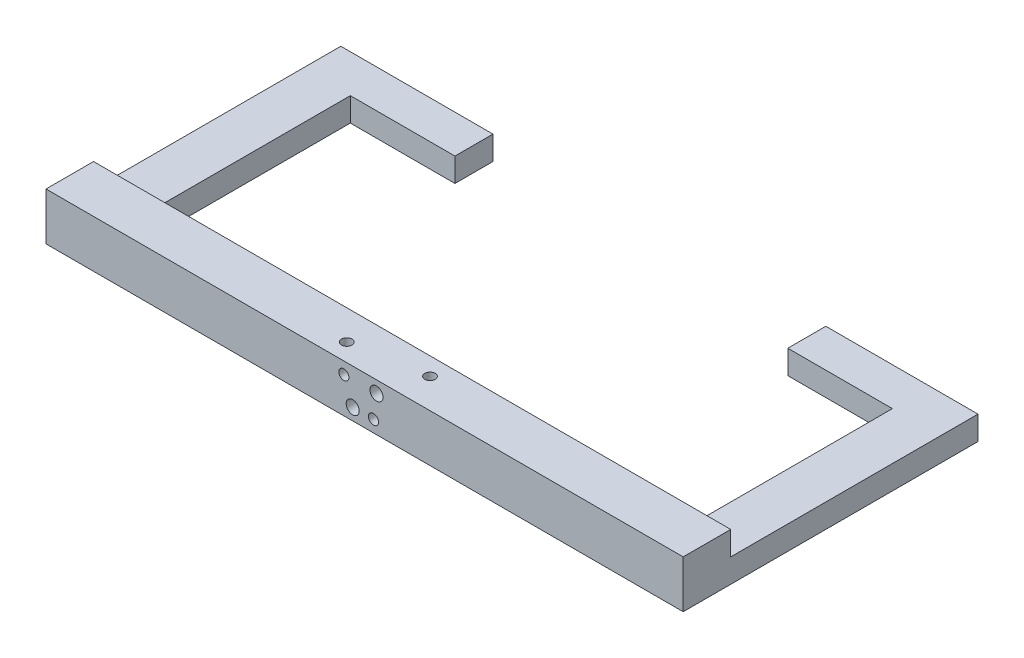
SolidWorks part; units mm, degrees
ref_plane "Front Plane" through (0, 0, 0) normal (0, 0, 1) x (1, 0, 0)
ref_plane "Top Plane" through (0, 0, 0) normal (0, 1, 0) x (1, 0, 0)
ref_plane "Right Plane" through (0, 0, 0) normal (1, 0, 0) x (0, 0, -1)
sketch "Sketch1" plane through (0, 0, 0) normal (0, 1, 0) x (1, 0, 0)
  line L0 (40.64, 68.58) -> (12.7, 68.58)
  line L7 (0, 78.74) -> (40.64, 78.74)
  line L8 (40.64, 68.58) -> (40.64, 78.74)
  line L9 (12.7, 68.58) -> (12.7, 12.7)
  line L10 (85.09, 68.0691) -> (85.09, -12.197) construction
  line L18 (12.7, 12.7) -> (157.48, 12.7)
  line L20 (0, 0) -> (170.18, 0)
  line L27 (0, 78.74) -> (0, 0)
  line L29 (170.18, 78.74) -> (170.18, 0)
  line L30 (157.48, 68.58) -> (157.48, 12.7)
  line L31 (129.54, 68.58) -> (129.54, 78.74)
  line L32 (170.18, 78.74) -> (129.54, 78.74)
  line L33 (129.54, 68.58) -> (157.48, 68.58)
  line L34 (97.79, 58.6145) -> (97.79, 33.6145) construction
  line L35 (72.39, 44.1997) -> (72.39, 23.8407) construction
  line L36 (12.7, 12.7) -> (0, 12.7)
  line L37 (157.48, 12.7) -> (170.18, 12.7)
  point P4 (85.09, 0)
  point P12 (85.09, 12.7)
  dimension "D1" = 10.16
  dimension "D2" = 157.48
  dimension "D3" = 55.88
  dimension "D4" = 12.7
  dimension "D5" = 40.64
  dimension "D6" = 12.7
  dimension "D7" = 12.7
  dimension "D8" = 12.7
extrude "Boss-Extrude2" add sketch "Sketch1" along normal blind 6.35 contours L18 L10 L20 L29 L32 L31 L33 L30 | L10 L18 L9 L0 L8 L7 L27 L20 region at (11.4884, 0, -52.7853) region at (158.6916, 0, -52.7853)
extrude "Boss-Extrude3" add sketch "Sketch1<3>" along normal blind 12.7 contours L37 L18 L36 L27 L20 L29 region at (85.09, 0, -6.35)
sketch "Sketch1<3>" plane through (0, 0, 0) normal (0, 1, 0) x (1, 0, 0) same geometry as "Sketch1"
sketch "Sketch3" plane through (0, 12.7, 0) normal (0, 1, 0) x (1, 0, 0)
  line L0 (0, 6.35) -> (170.18, 6.35) construction
  line L1 (0, 12.7) -> (0, 0) construction
  line L2 (170.18, 12.7) -> (170.18, 0) construction
  line L3 (0, 0) -> (170.18, 0) construction
  line L4 (72.39, 12.7) -> (97.79, 12.7) construction
  line L5 (72.39, 12.7) -> (72.39, 0) construction
  line L6 (72.39, 0) -> (97.79, 0) construction
  line L7 (97.79, 12.7) -> (97.79, 0) construction
  line L8 (72.39, 12.7) -> (97.79, 0) construction
  line L9 (72.39, 0) -> (97.79, 12.7) construction
  circle A0 centre (75.565, 7.9375) radius 1.397 construction
  circle A1 centre (94.615, 4.7625) radius 1.397 construction
  circle A2 centre (75.565, 4.7625) radius 1.397
  circle A3 centre (94.615, 7.9375) radius 1.397
  point P6 (85.09, 6.35)
  dimension "D2" = 2.794
  dimension "D1" = 25.4
  dimension "D3" = 3.175
  dimension "D4" = 1.5875
  dimension "D5" = 19.05
  dimension "D6" = 3.175
extrude "Cut-Extrude2" cut sketch "Sketch3" against normal up to next
sketch "Sketch4" plane through (0, 0, -12.7) normal (0, 0, -1) x (-1, 0, 0)
  line L0 (0, 12.7) -> (-170.18, 12.7) construction
  line L1 (-170.18, 12.7) -> (-170.18, 6.35) construction
  circle A0 centre (-87.4776, 3.175) radius 1.3525
  circle A1 centre (-79.5465, 9.525) radius 1.3525
  point P8 (-85.09, 12.7)
  point P9 (0, 0)
  dimension "D1" = 2.7051
  dimension "D4" = 6.35
  dimension "D2" = 9.525
  dimension "D3" = 82.7024
  dimension "D5" = 10.16
extrude "Cut-Extrude3" cut sketch "Sketch4" against normal up to next
sketch "Sketch5" plane through (0, 0, -12.7) normal (0, 0, -1) x (-1, 0, 0)
  line L0 (-78.74, 0) -> (-91.44, 12.7) construction
  line L1 (-88.265, 9.525) -> (-81.915, 3.175) construction
  line L3 (-12.7, 0) -> (-157.48, 0) construction
  line L4 (0, 12.7) -> (-170.18, 12.7) construction
  circle A0 centre (-88.265, 9.525) radius 1.75
  circle A1 centre (-81.915, 3.175) radius 1.75
  point P0 (-85.09, 12.7)
  point P8 (-85.09, 6.35)
  point P9 (-85.09, 6.35)
  point P10 (0, 0)
  point P11 (0, 0)
  dimension "D1" = 3.5
  dimension "D2" = 6.35
  dimension "D3" = 6.35
extrude "Cut-Extrude5" cut sketch "Sketch5" against normal blind 24
